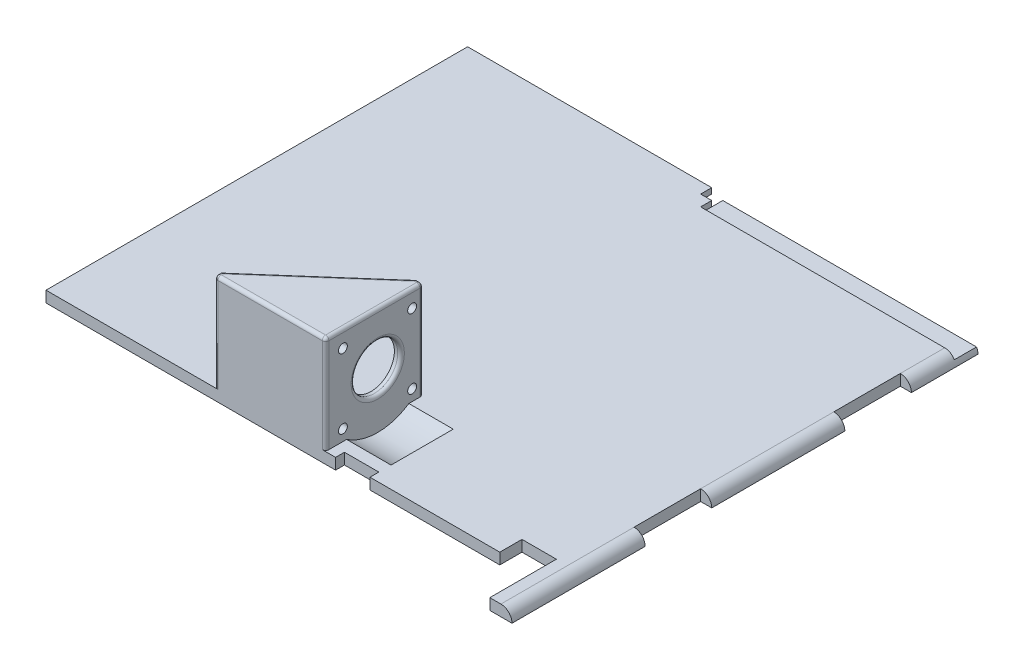
SolidWorks part; units mm, degrees
ref_plane "前基準面" through (0, 0, 0) normal (0, 0, 1) x (1, 0, 0)
ref_plane "上基準面" through (0, 0, 0) normal (0, 1, 0) x (1, 0, 0)
ref_plane "右基準面" through (0, 0, 0) normal (1, 0, 0) x (0, 0, -1)
sketch "草圖1" plane through (0, 0, 0) normal (0, 1, 0) x (1, 0, 0)
  line L0 (-36.2537, 43.5351) -> (203.7463, 43.5351)
  line L1 (203.7463, 43.5351) -> (203.7463, -286.4649)
  line L2 (198.7463, -286.4649) -> (198.7463, -256.4649)
  line L3 (198.7463, -256.4649) -> (183.2463, -256.4649)
  line L4 (183.2463, -256.4649) -> (183.2463, -266.4649)
  line L5 (183.2463, -266.4649) -> (124.7463, -266.4649)
  line L6 (124.7463, -266.4649) -> (124.7463, -262.4649)
  line L7 (124.7463, -262.4649) -> (109.2463, -262.4649)
  line L8 (109.2463, -262.4649) -> (109.2463, -266.4649)
  line L9 (109.2463, -266.4649) -> (-21.2537, -266.4649)
  line L10 (-21.2537, -266.4649) -> (-21.2537, 38.5351)
  line L11 (-21.2537, 38.5351) -> (-36.2537, 38.5351)
  line L12 (-36.2537, 38.5351) -> (-36.2537, 43.5351)
  line L13 (198.7463, -286.4649) -> (203.7463, -286.4649)
  line L15 (203.7463, -286.4649) -> (208.7463, -286.4649)
  line L16 (203.7463, -286.4649) -> (203.7463, -226.4649)
  line L17 (203.7463, -226.4649) -> (208.7463, -226.4649)
  line L18 (208.7463, -286.4649) -> (208.7463, -226.4649)
  line L19 (-36.2537, 43.5351) -> (-6.2537, 43.5351)
  line L20 (-36.2537, 43.5351) -> (-36.2537, 48.5351)
  line L21 (-36.2537, 48.5351) -> (-6.2537, 48.5351)
  line L22 (-6.2537, 43.5351) -> (-6.2537, 48.5351)
  line L23 (203.7463, 43.5351) -> (173.7463, 43.5351)
  line L24 (203.7463, 43.5351) -> (203.7463, 48.5351)
  line L25 (203.7463, 48.5351) -> (173.7463, 48.5351)
  line L26 (173.7463, 43.5351) -> (173.7463, 48.5351)
  line L27 (203.7463, 43.5351) -> (208.7463, 43.5351)
  line L28 (203.7463, 43.5351) -> (203.7463, -16.4649)
  line L29 (203.7463, -16.4649) -> (208.7463, -16.4649)
  line L30 (208.7463, 43.5351) -> (208.7463, -16.4649)
  line L31 (83.7463, 43.5351) -> (98.7463, 43.5351)
  line L32 (83.7463, 43.5351) -> (83.7463, 48.5351)
  line L33 (83.7463, 48.5351) -> (98.7463, 48.5351)
  line L34 (98.7463, 43.5351) -> (98.7463, 48.5351)
  line L35 (83.7463, 43.5351) -> (68.7463, 43.5351)
  line L36 (83.7463, 43.5351) -> (83.7463, 48.5351)
  line L37 (83.7463, 48.5351) -> (68.7463, 48.5351)
  line L38 (68.7463, 43.5351) -> (68.7463, 48.5351)
  line L39 (203.7463, -46.4649) -> (208.7463, -46.4649)
  line L40 (203.7463, -46.4649) -> (203.7463, -106.4649)
  line L41 (203.7463, -106.4649) -> (208.7463, -106.4649)
  line L42 (208.7463, -46.4649) -> (208.7463, -106.4649)
  line L43 (203.7463, -136.4649) -> (208.7463, -136.4649)
  line L44 (203.7463, -136.4649) -> (203.7463, -196.4649)
  line L45 (203.7463, -196.4649) -> (208.7463, -196.4649)
  line L46 (208.7463, -136.4649) -> (208.7463, -196.4649)
  dimension "D3" = 5
  dimension "D1" = 240
  dimension "D2" = 330
  dimension "D4" = 15
  dimension "D5" = 130.5
  dimension "D6" = 4
  dimension "D7" = 4
  dimension "D8" = 15.5
  dimension "D9" = 58.5
  dimension "D10" = 10
  dimension "D11" = 15.5
  dimension "D12" = 30
  dimension "D13" = 5
  dimension "D14" = 60
  dimension "D15" = 5
  dimension "D16" = 5
  dimension "D17" = 30
  dimension "D18" = 5
  dimension "D19" = 30
  dimension "D20" = 60
  dimension "D21" = 5
  dimension "D22" = 5
  dimension "D23" = 15
  dimension "D24" = 5
  dimension "D25" = 15
  dimension "D26" = 60
  dimension "D27" = 5
  dimension "D28" = 30
  dimension "D29" = 60
  dimension "D30" = 5
  dimension "D31" = 30
  dimension "D32" = 30
extrude "填料-伸長1" add sketch "草圖1" along normal blind 5 contours L2 L13 L1 L0 L12 L11 L10 L9 L8 L7 L6 L5 L4 L3 | L15 L18 L17 L1 | L30 L27 L1 L29 | L26 L0 L24 L25 | L0 L22 L21 L20 | L32 L33 L34 L31 | L36 L37 L38 L35 | L46 L45 L44 L43 | L42 L41 L40 L39 region at (-21.2537, 0, -46.0351) region at (91.0303, 0, 111.0679) region at (188.7463, 0, -46.0351) region at (206.2463, 0, -13.5351) region at (206.2463, 0, 256.4649)
fillet "圓角1" radius 5 4 edges at (208.7463, 5, -13.5351) (208.7463, 5, 76.4649) (208.7463, 5, 166.4649) (208.7463, 5, 256.4649)
sketch "草圖2" plane through (0, 5, 0) normal (0, 1, 0) x (1, 0, 0)
  line L1 (-36.2537, 48.5351) -> (208.7463, 48.5351)
  line L2 (-36.2537, 48.5351) -> (-36.2537, -76.4649)
  line L3 (-36.2537, -76.4649) -> (208.7463, -76.4649)
  line L4 (208.7463, 48.5351) -> (208.7463, -76.4649)
  dimension "D1" = 125
extrude "除料-伸長1" cut sketch "草圖2" against normal blind 5
sketch "草圖3" plane through (0, 0, 76.4649) normal (0, 0, -1) x (-1, 0, 0)
  line L1 (21.2537, 0) -> (-88.7463, 0)
  line L2 (21.2537, 0) -> (21.2537, 2.5)
  line L3 (21.2537, 2.5) -> (-88.7463, 2.5)
  line L4 (-88.7463, 0) -> (-88.7463, 2.5)
  line L5 (-93.7463, 2.5) -> (-208.7463, 2.5)
  line L6 (-93.7463, 2.5) -> (-93.7463, 5)
  line L7 (-93.7463, 5) -> (-208.7463, 5)
  line L8 (-208.7463, 2.5) -> (-208.7463, 5)
  point P9 (-93.7463, 3.75)
  dimension "D1" = 2.5
  dimension "D2" = 110
  dimension "D3" = 2.5
  dimension "D4" = 115
  dimension "D5" = 5
extrude "除料-伸長2" cut sketch "草圖3" against normal blind 10
sketch "草圖4" plane through (0, 0, 76.4649) normal (0, 0, -1) x (-1, 0, 0)
  line L1 (-93.7463, 5) -> (-88.7463, 5)
  line L2 (-93.7463, 5) -> (-93.7463, 0)
  line L3 (-93.7463, 0) -> (-88.7463, 0)
  line L4 (-88.7463, 5) -> (-88.7463, 0)
extrude "除料-伸長3" cut sketch "草圖4" against normal blind 5
sketch "草圖5" plane through (0, 0, 266.4649) normal (0, 0, 1) x (1, 0, 0)
  line L1 (104.7463, 5) -> (54.7463, 5)
  line L2 (104.7463, 5) -> (104.7463, 49)
  line L3 (104.7463, 49) -> (54.7463, 49)
  line L4 (54.7463, 5) -> (54.7463, 49)
  line L5 (124.7463, 5) -> (124.7463, 0) construction
  dimension "D1" = 50
  dimension "D2" = 44
  dimension "D3" = 20
extrude "填料-伸長2" add sketch "草圖5" against normal blind 47 contours L2 L1 L4 L3
sketch "草圖6" plane through (54.7463, 0, 0) normal (-1, 0, 0) x (0, 0, 1)
  line L0 (219.4649, 49) -> (266.4649, 49) construction
  line L1 (222.2649, 46.4) -> (263.6649, 46.4)
  line L2 (222.2649, 46.4) -> (222.2649, 5)
  line L3 (222.2649, 5) -> (263.6649, 5)
  line L4 (263.6649, 46.4) -> (263.6649, 5)
  line L5 (219.4649, 5) -> (219.4649, 49) construction
  line L6 (266.4649, 5) -> (266.4649, 49) construction
  line L7 (266.4649, 5) -> (76.4649, 5) construction
  dimension "D1" = 2.6
  dimension "D2" = 2.8
  dimension "D3" = 2.8
  dimension "D4" = 0
extrude "除料-伸長4" cut sketch "草圖6" against normal blind 47 contours L2 L1 L4 L3
sketch "草圖7" plane through (101.7463, 0, 0) normal (-1, 0, 0) x (0, 0, 1)
  line L0 (263.6649, 46.4) -> (263.6649, 5) construction
  line L1 (222.2649, 46.4) -> (263.6649, 46.4) construction
  line L2 (222.2649, 46.4) -> (222.2649, 5) construction
  line L5 (263.6649, 46.4) -> (263.6649, 5) construction
  circle A0 centre (242.9649, 25.7) radius 10.5
  dimension "D1" = 41.4
  dimension "D4" = 21
  dimension "D2" = 20.7
  dimension "D3" = 20.7
extrude "除料-伸長5" cut sketch "草圖7" against normal through all
sketch "草圖8" plane through (0, 49, 0) normal (0, 1, 0) x (1, 0, 0)
  line L4 (54.7463, -263.6649) -> (101.7463, -222.4649)
  line L8 (104.7463, -219.4649) -> (54.7463, -219.4649) construction
  line L9 (54.7463, -263.6649) -> (54.7463, -219.4649)
  line L13 (104.7463, -219.4649) -> (54.7463, -219.4649)
  line L14 (101.7463, -222.4649) -> (104.7463, -222.4649)
  line L15 (104.7463, -219.4649) -> (104.7463, -266.4649) construction
  line L16 (104.7463, -222.4649) -> (104.7463, -219.4649)
  dimension "D2" = 3
extrude "除料-伸長6" cut sketch "草圖8" against normal blind 44
sketch "草圖10" plane through (101.7463, 0, 0) normal (-1, 0, 0) x (0, 0, 1)
  line L0 (222.4649, 46.4) -> (263.6649, 46.4) construction
  line L1 (222.4649, 5) -> (222.4649, 46.4) construction
  line L2 (222.4649, 46.4) -> (263.6649, 46.4) construction
  line L3 (263.6649, 46.4) -> (263.6649, 5) construction
  line L4 (266.4649, 5) -> (76.4649, 5) construction
  line L5 (222.4649, 5) -> (263.6649, 5) construction
  circle A0 centre (227.4649, 41.4) radius 2
  circle A1 centre (258.6649, 41.4) radius 2
  circle A2 centre (258.6649, 10) radius 2
  circle A3 centre (227.4649, 10) radius 2
  dimension "D1" = 4
  dimension "D2" = 4
  dimension "D3" = 4
  dimension "D4" = 4
  dimension "D5" = 5
  dimension "D6" = 5
  dimension "D7" = 5
  dimension "D8" = 5
  dimension "D9" = 5
  dimension "D10" = 5
  dimension "D11" = 5
  dimension "D12" = 5
extrude "除料-伸長7" cut sketch "草圖10" against normal through all
sketch "草圖13" plane through (104.7463, 0, 0) normal (1, 0, 0) x (0, 0, -1)
  circle A0 centre (-242.9649, 25.7) radius 25
  dimension "D1" = 50
extrude "除料-伸長9" cut sketch "草圖13" along normal blind 20
fillet "圓角11" radius 1.497 9 edges at (104.7463, 49, 244.4649) (79.7463, 49, 266.4649) (54.7463, 49, 265.0649) (78.2463, 49, 243.0649) (103.2463, 49, 222.4649) (54.7463, 27, 266.4649) (104.7463, 27, 266.4649) (104.7463, 25.7, 232.4649) (104.7463, 27, 222.4649)
equation "\"1.5.0000mm\"=10"
